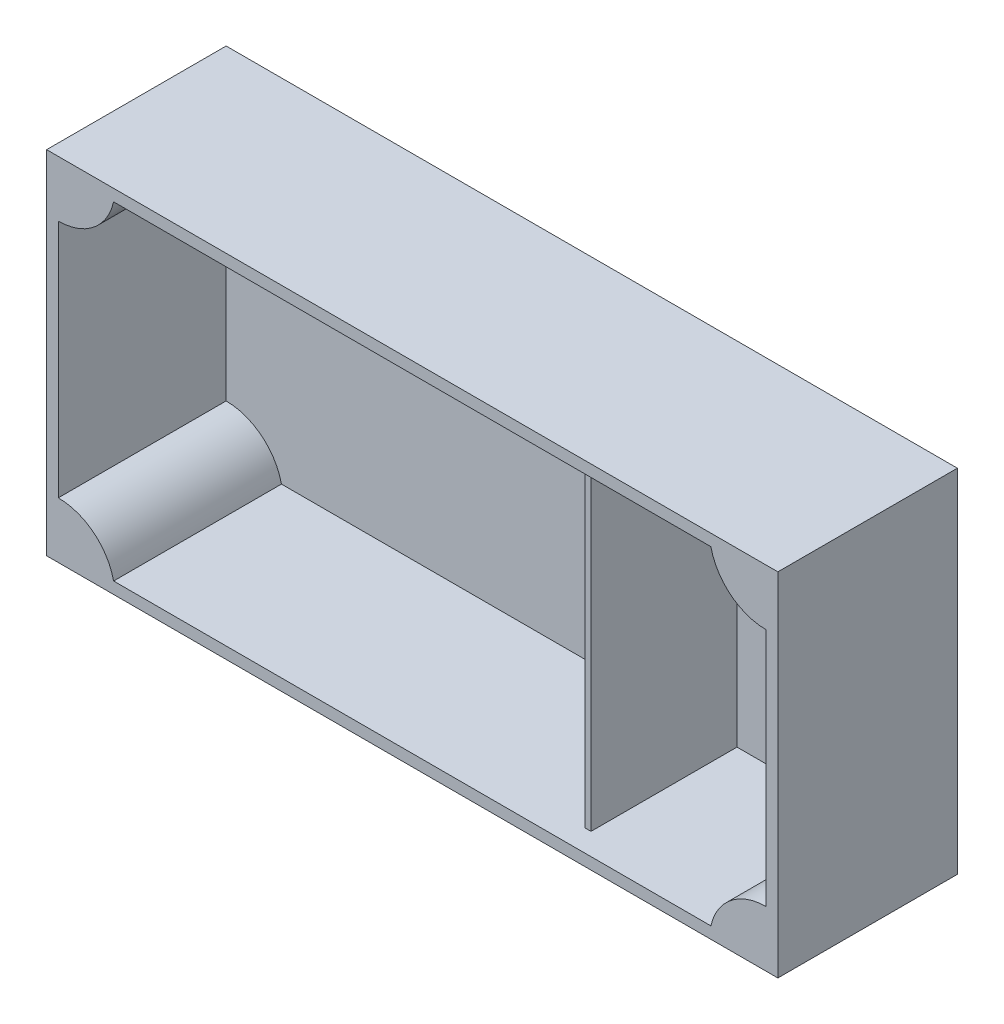
SolidWorks part; units mm, degrees
ref_plane "Plan de face" through (0, 0, 0) normal (0, 0, 1) x (1, 0, 0)
ref_plane "Plan de dessus" through (0, 0, 0) normal (0, 1, 0) x (1, 0, 0)
ref_plane "Plan de droite" through (0, 0, 0) normal (1, 0, 0) x (0, 0, -1)
sketch "Esquisse1" plane through (0, 0, 0) normal (0, 0, 1) x (1, 0, 0)
  line L1 (-48.5, 22.5) -> (48.5, 22.5)
  line L2 (-48.5, 22.5) -> (-48.5, -22.5)
  line L3 (-48.5, -22.5) -> (48.5, -22.5)
  line L4 (48.5, 22.5) -> (48.5, -22.5)
  line L5 (-48.5, 22.5) -> (48.5, -22.5) construction
  line L6 (-48.5, -22.5) -> (48.5, 22.5) construction
  point P0 (0, 0)
  dimension "D1" = 97
  dimension "D2" = 45
extrude "Boss.-Extru.1" add sketch "Esquisse1" along normal blind 23
shell "Coque1" thickness 1.6 removed face at (0, 0, 23) outward yes
ref_plane "Plan1" through (0, 0, 20) normal (0, 0, 1) x (1, 0, 0)
sketch "Esquisse8" plane through (0, 0, 20) normal (0, 0, 1) x (1, 0, 0)
  line L0 (21.5, 16.8946) -> (21.5, -12.3256)
  line L1 (48.5, -22.5) -> (48.5, 22.5) construction
  dimension "D1" = 27
rib "Nervure18" sketch "Esquisse8" sketch "Esquisse8" thickness 0.8 extrusion direction normal to sketch draft on no parameters "D1"=0.8
sketch "Esquisse10" plane through (0, 0, 0) normal (0, 0, 1) x (1, 0, 0)
  line L0 (-48.5, 22.5) -> (-48.5, 16.4211)
  line L1 (-48.5, 22.5) -> (-48.5, -22.5) construction
  line L2 (20.7, 22.5) -> (-48.5, 22.5) construction
  line L3 (-40.9211, 22.5) -> (-48.5, 22.5)
  arc A0 (-48.5, 16.4211) -> (-40.9211, 22.5) centre (-48.5, 24.1851) ccw
extrude "Boss.-Extru.2" add sketch "Esquisse10" along normal up to surface (23 mm away) up to face at (0, 0, 23)
mirror "Symétrie1" about plane through (0, 0, 0) normal (1, 0, 0) of "Boss.-Extru.2"
mirror "Symétrie2" about plane through (0, 0, 0) normal (0, 1, 0) of "Boss.-Extru.2"
mirror "Symétrie3" about plane through (0, 0, 0) normal (0, 1, 0) of "Symétrie1"
equation "\"buse\"= 0.8"
equation "\"D1@Coque1\"=\"buse\"*2"
equation "\"hauteur\"=10"
equation "\"D1@Nervure1\"=\"hauteur\""
equation "\"D1@Nervure18\"=\"buse\""
